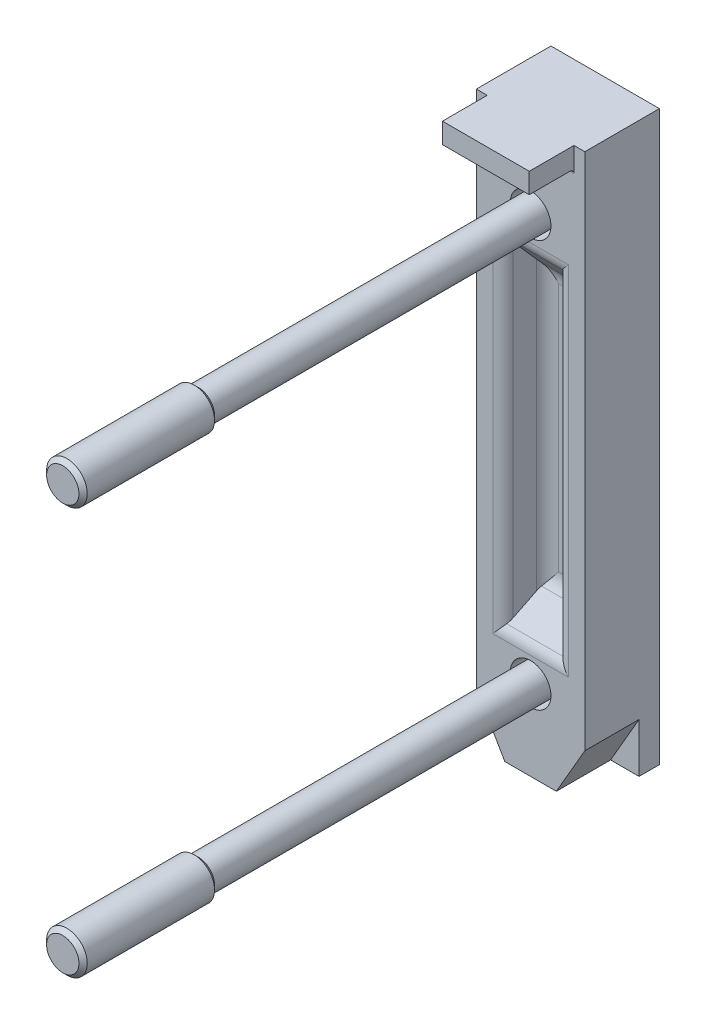
SolidWorks part; units mm, degrees
ref_plane "Front Plane" through (0, 0, 0) normal (0, 0, 1) x (1, 0, 0)
ref_plane "Top Plane" through (0, 0, 0) normal (0, 1, 0) x (1, 0, 0)
ref_plane "Right Plane" through (0, 0, 0) normal (1, 0, 0) x (0, 0, -1)
ref_plane "Plane1" through (0, 0, 0) normal (1, 0, 0) x (0, 0, -1)
sketch "Sketch1" plane through (0, 0, 0) normal (1, 0, 0) x (0, 0, -1)
  line L0 (0, 36) -> (0, -5.9)
  line L1 (0, -5.9) -> (5.5, -5.9)
  line L2 (5.5, -5.9) -> (5.5, 36)
  line L3 (5.5, 36) -> (0, 36)
extrude "Boss-Extrude1" add sketch "Sketch1" against normal blind 4 and the other way blind 4
ref_plane "Plane2" through (0, 0, 0) normal (1, 0, 0) x (0, 0, -1)
sketch "Sketch2" plane through (0, 0, 0) normal (1, 0, 0) x (0, 0, -1)
  line L0 (-3.3, 34.5) -> (-0.3, 34.5)
  line L1 (0, 34.2) -> (0, 36)
  line L2 (0, 36) -> (-3.3, 36)
  line L3 (-3.3, 36) -> (-3.3, 34.5)
  arc A0 (-0.3, 34.5) -> (0, 34.2) centre (-0.3, 34.2) cw
extrude "Boss-Extrude2" add sketch "Sketch2" against normal blind 3.2 and the other way blind 3.2
ref_plane "Plane3" through (0, 0, 0) normal (1, 0, 0) x (0, 0, -1)
sketch "Sketch3" plane through (0, 0, 0) normal (1, 0, 0) x (0, 0, -1)
  line L0 (0, 30) -> (0, 31.5)
  line L1 (0, 31.5) -> (2.4, 31.5)
  line L2 (2.4, 31.5) -> (2.4, 33)
  line L3 (2.4, 33) -> (5.5, 33)
  line L4 (5.5, 33) -> (5.5, 30)
  line L5 (5.5, 30) -> (0, 30)
  line L6 (5.5, 30) -> (0, 30) construction
revolve "Cut-Revolve1" cut sketch "Sketch3" angle 360 about L6 reverse direction yes
ref_plane "Plane4" through (0, 0, 0) normal (1, 0, 0) x (0, 0, -1)
sketch "Sketch4" plane through (0, 0, 0) normal (1, 0, 0) x (0, 0, -1)
  line L0 (0, 0) -> (0, 1.5)
  line L1 (0, 1.5) -> (2.4, 1.5)
  line L2 (2.4, 1.5) -> (2.4, 3)
  line L3 (2.4, 3) -> (5.5, 3)
  line L4 (5.5, 3) -> (5.5, 0)
  line L5 (5.5, 0) -> (0, 0)
  line L6 (5.5, 0) -> (0, 0) construction
revolve "Cut-Revolve2" cut sketch "Sketch4" angle 360 about L6 reverse direction yes
ref_plane "Plane5" through (0, 15, 0) normal (0, 1, 0) x (1, 0, 0)
sketch "Sketch5" plane through (0, 15, 0) normal (0, 1, 0) x (1, 0, 0)
  line L0 (-3.5, -2.4) -> (3.5, -2.4)
  line L1 (3.5, -2.4) -> (3.5, 0)
  line L2 (3.5, 0) -> (2.7871, 0)
  line L3 (1.8808, 0.5774) -> (1.327, 1.7649)
  line L4 (0.3301, 2.4) -> (-0.3301, 2.4)
  line L5 (-1.327, 1.7649) -> (-1.8808, 0.5774)
  line L6 (-2.7871, 0) -> (-3.5, 0)
  line L7 (-3.5, 0) -> (-3.5, -2.4)
  arc A0 (2.7871, 0) -> (1.8808, 0.5774) centre (2.7871, 1) cw
  arc A1 (1.327, 1.7649) -> (0.3301, 2.4) centre (0.3301, 1.3) ccw
  arc A2 (-0.3301, 2.4) -> (-1.327, 1.7649) centre (-0.3301, 1.3) ccw
  arc A3 (-1.8808, 0.5774) -> (-2.7871, 0) centre (-2.7871, 1) cw
extrude "Cut-Extrude1" cut sketch "Sketch5" against normal blind 13.2 and the other way blind 13.2
ref_plane "Plane6" through (0, 0, 0) normal (1, 0, 0) x (0, 0, -1)
sketch "Sketch6" plane through (0, 0, 0) normal (1, 0, 0) x (0, 0, -1)
  line L0 (0, 1.6268) -> (2.4, 1.6268)
  line L1 (2.4, 1.6268) -> (2.4, 5.7972)
  line L2 (1.9906, 4.6723) -> (0.3041, 2.6625)
  line L3 (0, 1.8268) -> (0, 1.6268)
  arc A0 (2.4, 5.7972) -> (1.9906, 4.6723) centre (0.65, 5.7972) cw
  arc A1 (0.3041, 2.6625) -> (0, 1.8268) centre (1.3, 1.8268) ccw
extrude "Boss-Extrude3" add sketch "Sketch6" against normal blind 2.85 and the other way blind 2.85
ref_plane "Plane7" through (0, 0, 0) normal (1, 0, 0) x (0, 0, -1)
sketch "Sketch7" plane through (0, 0, 0) normal (1, 0, 0) x (0, 0, -1)
  line L0 (0, 28.3732) -> (0, 28.1732)
  line L1 (0.3041, 27.3375) -> (1.9906, 25.3277)
  line L2 (2.4, 24.2028) -> (2.4, 28.3732)
  line L3 (2.4, 28.3732) -> (0, 28.3732)
  arc A0 (0, 28.1732) -> (0.3041, 27.3375) centre (1.3, 28.1732) ccw
  arc A1 (1.9906, 25.3277) -> (2.4, 24.2028) centre (0.65, 24.2028) cw
extrude "Boss-Extrude4" add sketch "Sketch7" against normal blind 2.85 and the other way blind 2.85
ref_plane "Plane8" through (0, 0, 0) normal (0, 0, 1) x (1, 0, 0)
sketch "Sketch8" plane through (0, 0, 0) normal (0, 0, 1) x (1, 0, 0)
  line L0 (-15, -15.2643) -> (16.0738, -15.2643)
  line L1 (16.0738, -15.2643) -> (16.0738, -1.5699)
  line L2 (16.0738, -1.5699) -> (4.4, -1.5699)
  line L3 (4.4, -1.5699) -> (1.9, -5.9)
  line L4 (1.9, -5.9) -> (-1.9, -5.9)
  line L5 (-1.9, -5.9) -> (-4.4, -1.5699)
  line L6 (-4.4, -1.5699) -> (-15, -1.5699)
  line L7 (-15, -1.5699) -> (-15, -15.2643)
extrude "Cut-Extrude2" cut sketch "Sketch8" against normal blind 4
ref_plane "Plane9" through (0, 0, 0) normal (1, 0, 0) x (0, 0, -1)
sketch "Sketch9" plane through (0, 0, 0) normal (1, 0, 0) x (0, 0, -1)
  line L0 (-34.5, 30) -> (-34.5, 31.1935)
  line L1 (-34.5, 31.1935) -> (-34.1935, 31.5)
  line L2 (-34.1935, 31.5) -> (-24.8065, 31.5)
  line L3 (-24.8065, 31.5) -> (-24.5, 31.1935)
  line L4 (-24.5, 31.1935) -> (2.4, 31.1935)
  line L5 (2.4, 31.1935) -> (2.4, 32.6)
  line L6 (2.4, 32.6) -> (4.5, 32.6)
  line L7 (4.5, 32.6) -> (4.5, 30)
  line L8 (4.5, 30) -> (-34.5, 30)
  line L9 (4.5, 30) -> (-34.5, 30) construction
revolve "Revolve1" add sketch "Sketch9" angle 360 about L9 reverse direction yes
cosmetic thread "Cosmetic Thread1" parameters "D1"=10, "D2"=2.387
ref_plane "Plane10" through (0, 0, 0) normal (1, 0, 0) x (0, 0, -1)
sketch "Sketch10" plane through (0, 0, 0) normal (1, 0, 0) x (0, 0, -1)
  line L0 (-34.5, 0) -> (-34.5, 1.1935)
  line L1 (-34.5, 1.1935) -> (-34.1935, 1.5)
  line L2 (-34.1935, 1.5) -> (-24.8065, 1.5)
  line L3 (-24.8065, 1.5) -> (-24.5, 1.1935)
  line L4 (-24.5, 1.1935) -> (2.4, 1.1935)
  line L5 (2.4, 1.1935) -> (2.4, 2.6)
  line L6 (2.4, 2.6) -> (4.5, 2.6)
  line L7 (4.5, 2.6) -> (4.5, 0)
  line L8 (4.5, 0) -> (-34.5, 0)
  line L9 (4.5, 0) -> (-34.5, 0) construction
revolve "Revolve2" add sketch "Sketch10" angle 360 about L9 reverse direction yes
cosmetic thread "Cosmetic Thread2" parameters "D1"=10, "D2"=2.387
ref_plane "Plane11" through (0, 0, -4.5) normal (0, 0, -1) x (-1, 0, 0)
sketch "Sketch11" plane through (0, 0, -4.5) normal (0, 0, -1) x (-1, 0, 0)
  line L0 (0.5, 28) -> (0.5, 29.5)
  line L1 (0.5, 29.5) -> (2, 29.5)
  line L2 (2, 29.5) -> (2, 30.5)
  line L3 (2, 30.5) -> (0.5, 30.5)
  line L4 (0.5, 30.5) -> (0.5, 32)
  line L5 (0.5, 32) -> (-0.5, 32)
  line L6 (-0.5, 32) -> (-0.5, 30.5)
  line L7 (-0.5, 30.5) -> (-2, 30.5)
  line L8 (-2, 30.5) -> (-2, 29.5)
  line L9 (-2, 29.5) -> (-0.5, 29.5)
  line L10 (-0.5, 29.5) -> (-0.5, 28)
  line L11 (-0.5, 28) -> (0.5, 28)
extrude "Cut-Extrude3" cut sketch "Sketch11" against normal blind 1.5 and the other way blind 1.5
ref_plane "Plane12" through (0, 0, -4.5) normal (0, 0, -1) x (-1, 0, 0)
sketch "Sketch12" plane through (0, 0, -4.5) normal (0, 0, -1) x (-1, 0, 0)
  line L0 (0.5, -2) -> (0.5, -0.5)
  line L1 (0.5, -0.5) -> (2, -0.5)
  line L2 (2, -0.5) -> (2, 0.5)
  line L3 (2, 0.5) -> (0.5, 0.5)
  line L4 (0.5, 0.5) -> (0.5, 2)
  line L5 (0.5, 2) -> (-0.5, 2)
  line L6 (-0.5, 2) -> (-0.5, 0.5)
  line L7 (-0.5, 0.5) -> (-2, 0.5)
  line L8 (-2, 0.5) -> (-2, -0.5)
  line L9 (-2, -0.5) -> (-0.5, -0.5)
  line L10 (-0.5, -0.5) -> (-0.5, -2)
  line L11 (-0.5, -2) -> (0.5, -2)
extrude "Cut-Extrude4" cut sketch "Sketch12" against normal blind 1.5 and the other way blind 1.5
